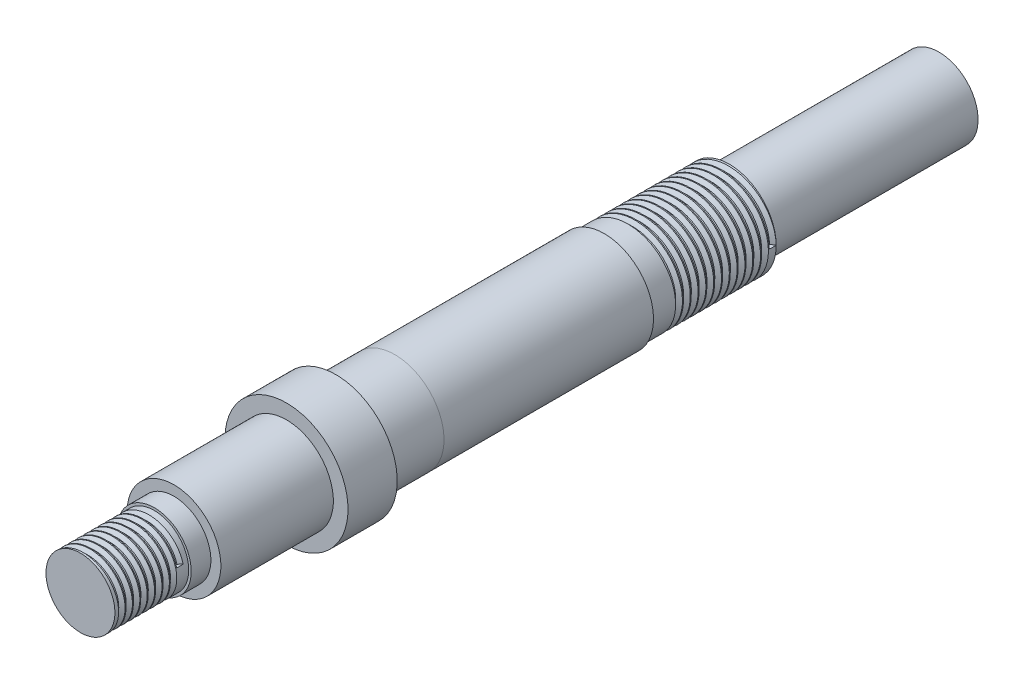
SolidWorks part; units mm, degrees
ref_plane "Front Plane" through (0, 0, 0) normal (0, 0, 1) x (1, 0, 0)
ref_plane "Top Plane" through (0, 0, 0) normal (0, 1, 0) x (1, 0, 0)
ref_plane "Right Plane" through (0, 0, 0) normal (1, 0, 0) x (0, 0, -1)
sketch "Derived Spindle Sketch" plane through (0, 0, 0) normal (1, 0, 0) x (0, 0, -1)
  line L0 (141.5523, 0) -> (-87.5573, 0)
  line L1 (93.1469, 36.5125) -> (0, 36.5125) construction
  line L2 (93.1469, 36.5125) -> (93.1469, -36.5125) construction
  line L3 (93.1469, -36.5125) -> (0, -36.5125) construction
  line L4 (0, 36.5125) -> (0, -36.5125) construction
  line L5 (0, 36.5125) -> (-15.24, 36.5125) construction
  line L6 (0, 36.5125) -> (0, -36.5125) construction
  line L7 (0, -36.5125) -> (-15.24, -36.5125) construction
  line L8 (-15.24, 36.5125) -> (-15.24, -36.5125) construction
  line L9 (-22.86, 9.525) -> (0, 9.525)
  line L10 (-22.86, 9.525) -> (-22.86, -9.525)
  line L11 (-22.86, -9.525) -> (0, -9.525)
  line L12 (0, 9.525) -> (0, -9.525)
  line L13 (22, 10.0076) -> (10, 10.0076)
  line L14 (22, 10.0076) -> (22, -10.0076)
  line L15 (22, -10.0076) -> (10, -10.0076)
  line L16 (10, 10.0076) -> (10, -10.0076)
  line L17 (64.5719, 9.9949) -> (52.5719, 9.9949)
  line L18 (64.5719, 9.9949) -> (64.5719, -9.9949)
  line L19 (64.5719, -9.9949) -> (52.5719, -9.9949)
  line L20 (52.5719, 9.9949) -> (52.5719, -9.9949)
  line L22 (52.5719, 9.9949) -> (22, 9.9949)
  line L23 (52.5719, 9.9949) -> (52.5719, -9.9949)
  line L24 (52.5719, -9.9949) -> (22, -9.9949)
  line L25 (22, 9.9949) -> (22, -9.9949)
  line L26 (64.5719, 9.525) -> (89.9719, 9.525)
  line L27 (64.5719, 9.525) -> (64.5719, -9.525)
  line L28 (64.5719, -9.525) -> (89.9719, -9.525)
  line L29 (89.9719, 9.525) -> (89.9719, -9.525)
  line L30 (115.1417, 7.9375) -> (132.5769, 7.9375)
  line L31 (115.1417, 7.9375) -> (115.1417, -7.9375)
  line L32 (115.1417, -7.9375) -> (132.5769, -7.9375)
  line L33 (132.5769, 7.9375) -> (132.5769, -7.9375)
  line L34 (10, 12.5) -> (0, 12.5)
  line L35 (10, 12.5) -> (10, -12.5)
  line L36 (10, -12.5) -> (0, -12.5)
  line L37 (0, 12.5) -> (0, -12.5)
  line L38 (-41.86, 7.0002) -> (-26.86, 7.0002)
  line L39 (-41.86, 7.0002) -> (-41.86, -7.0002)
  line L40 (-41.86, -7.0002) -> (-26.86, -7.0002)
  line L41 (-26.86, 7.0002) -> (-26.86, -7.0002)
  line L42 (93.1469, 36.5125) -> (104.5769, 36.5125) construction
  line L43 (93.1469, 36.5125) -> (93.1469, -36.5125) construction
  line L44 (93.1469, -36.5125) -> (104.5769, -36.5125) construction
  line L45 (104.5769, 36.5125) -> (104.5769, -36.5125) construction
  line L46 (115.1417, -7.9375) -> (89.9719, -7.9375)
  line L47 (115.1417, -7.9375) -> (115.1417, 7.9375)
  line L48 (115.1417, 7.9375) -> (89.9719, 7.9375)
  line L49 (89.9719, -7.9375) -> (89.9719, 7.9375)
  line L54 (-22.86, 7.5) -> (-26.86, 7.5)
  line L55 (-22.86, 7.5) -> (-22.86, -7.5)
  line L56 (-22.86, -7.5) -> (-26.86, -7.5)
  line L57 (-26.86, 7.5) -> (-26.86, -7.5)
revolve "Shaft Revolve" add sketch "Derived Spindle Sketch" angle 360 about L0 region at (0, 3.9687, -123.8593) region at (0, 3.9687, -102.5568) region at (0, 4.7625, -77.2719) region at (0, 4.9975, -58.5719) region at (0, 4.9975, -37.2859) region at (0, 5.0038, -16) region at (0, 6.25, -5) region at (0, 4.7625, 11.43) region at (0, 3.75, 24.86) region at (0, 3.5001, 34.36)
thread "M14x1 thread" pitch 1.5 method cut profile "Thread Profile1" start angle 0, offset 0, length 12.7, pitch 1.5, diameter 14.0005
ref_plane "Plane1" through (-7.0002, 0, 41.86) normal (0, -1, 0) x (-1, 0, 0)
sketch "Thread Profile1" plane through (-7.0002, 0, 41.86) normal (0, -1, 0) x (-1, 0, 0)
  line L0 (0, 0) -> (0, 1.5) construction
  line L11 (0, 0) -> (0, 1.3125)
  line L12 (0, 1.3125) -> (-0.8119, 0.8437)
  line L13 (-0.8119, 0.8437) -> (-0.8119, 0.4687)
  line L15 (-0.8119, 0.4687) -> (0, 0)
  line L17 (-0.8119, 0.6562) -> (0, 0.6562) construction
  point P2 (0, 0)
  dimension "Pitch" = 1.5
  dimension "Profile_Angle" = 60
  dimension "Profile_Land" = 0.375
  dimension "Profile_Height" = 0.8119
thread "3/4-16 thread" pitch 1.5875 method cut profile "Thread Profile2" start angle 0, offset 0, length 20.32, pitch 1.5875, diameter 19.05
ref_plane "Plane2" through (9.525, 0, -89.9719) normal (0, -1, 0) x (1, 0, 0)
sketch "Thread Profile2" plane through (9.525, 0, -89.9719) normal (0, -1, 0) x (1, 0, 0)
  line L0 (0, 0) -> (0, 1.5875) construction
  line L11 (0, 0) -> (0, 1.3891)
  line L12 (0, 1.3891) -> (-0.8593, 0.893)
  line L13 (-0.8593, 0.893) -> (-0.8593, 0.4961)
  line L15 (-0.8593, 0.4961) -> (0, 0)
  line L17 (-0.8593, 0.6945) -> (0, 0.6945) construction
  point P2 (0, 0)
  dimension "Pitch" = 1.5875
  dimension "Profile_Angle" = 60
  dimension "Profile_Land" = 0.3969
  dimension "Profile_Height" = 0.8593
